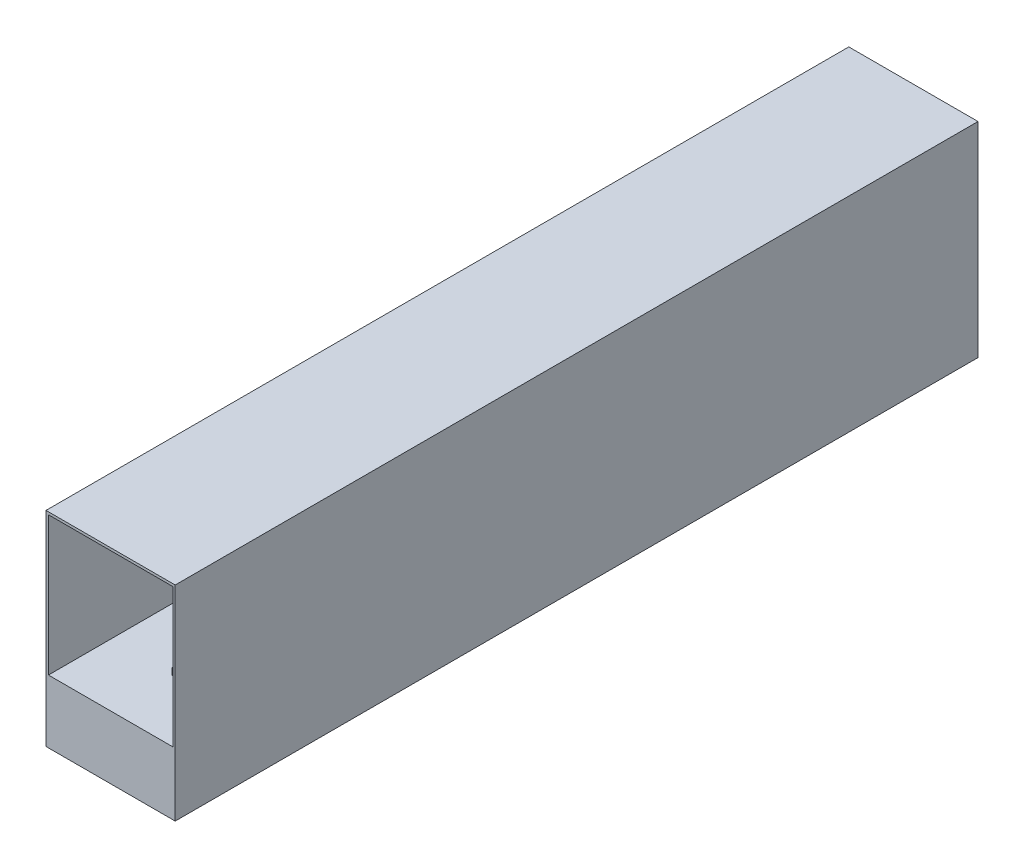
SolidWorks part; units mm, degrees
note: The reader was unsure of these and kept them because the rebuilt part matched: shared geometry of "Sketch1<4>".
material "Plain Carbon Steel"
ref_plane "Front Plane" through (0, 0, 0) normal (0, 0, 1) x (1, 0, 0)
ref_plane "Top Plane" through (0, 0, 0) normal (0, 1, 0) x (1, 0, 0)
ref_plane "Right Plane" through (0, 0, 0) normal (1, 0, 0) x (0, 0, -1)
sketch "Sketch1" plane through (0, 0, 0) normal (0, 0, 1) x (1, 0, 0)
  line L0 (1424.94, 0) -> (-1424.94, 0) construction
  line L1 (-1299.972, -1270) -> (1299.972, -1270)
  line L2 (-1299.972, -1270) -> (-1299.972, 2844.8)
  line L3 (-1299.972, 2844.8) -> (1299.972, 2844.8)
  line L4 (1299.972, -1270) -> (1299.972, 2844.8)
  line L5 (-1250.95, 2794) -> (1250.95, 2794)
  line L6 (-1250.95, 2794) -> (-1250.95, 0)
  line L7 (-1250.95, 0) -> (1250.95, 0)
  line L8 (1250.95, 2794) -> (1250.95, 0)
  line L12 (0, 3048) -> (0, -1524) construction
  point P10 (0, -1270)
  point P14 (0, 0)
  dimension "D1" = 2599.944
  dimension "D2" = 4114.8
  dimension "D3" = 2501.9
  dimension "D4" = 2794
  dimension "D5" = 1270
extrude "exterior" add sketch "Sketch1" against normal mid plane 16154.4 contours L3 L4 L1 L2
extrude "interior" cut sketch "Sketch1<4>" against normal mid plane 16002 contours L7 L8 L5 L6
sketch "Sketch1<4>" plane through (0, 0, 0) normal (0, 0, 1) x (1, 0, 0) same geometry as "Sketch1"
sketch "Sketch3" plane through (0, 0, 8077.2) normal (0, 0, 1) x (1, 0, 0)
  line L1 (-1250.95, 2794) -> (1250.95, 2794)
  line L2 (-1250.95, 2794) -> (-1250.95, 0)
  line L3 (-1250.95, 0) -> (1250.95, 0)
  line L4 (1250.95, 2794) -> (1250.95, 0)
  point P4 (0, 0)
  dimension "D1" = 2501.9
  dimension "D2" = 2794
extrude "opening" cut sketch "Sketch3" against normal up to next
sketch "floor centerline" plane through (0, 0, 0) normal (0, 1, 0) x (1, 0, 0)
  line L0 (0, -6858) -> (0, 6756.4) construction
sketch "center wall" plane through (0, 0, 0) normal (1, 0, 0) x (0, 0, -1)
  line L2 (8001, 0) -> (-8077.2, 0) construction
  line L4 (-6790.4216, 137.0252) -> (-6841.6304, 137.0252)
  line L5 (-6790.4216, 137.0252) -> (-6790.4216, 0)
  line L6 (-6790.4216, 0) -> (-6841.6304, 0)
  line L7 (-6841.6304, 137.0252) -> (-6841.6304, 0)
surface "center plane" sketch "center wall"
